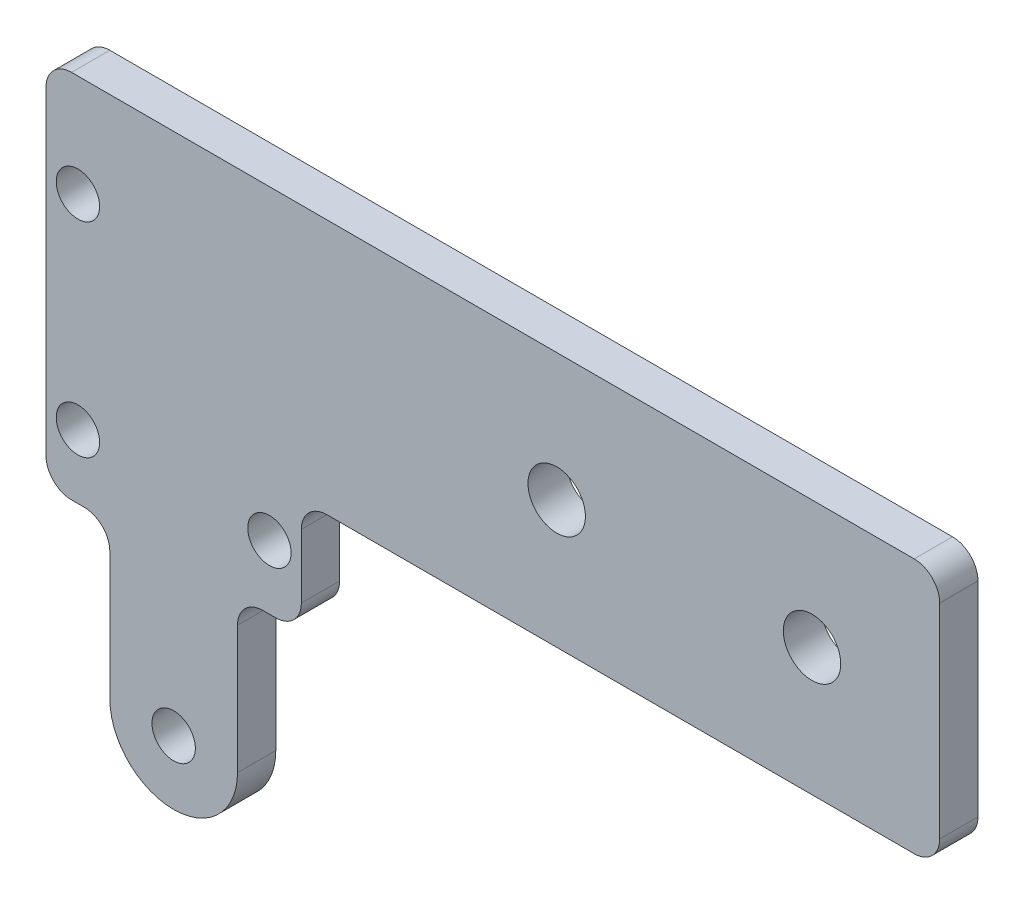
SolidWorks part; units mm, degrees
material "1023 Kohlenstoffstahlblech (SS)"
ref_plane "Ebene vorne" through (0, 0, 0) normal (0, 0, 1) x (1, 0, 0)
ref_plane "Ebene oben" through (0, 0, 0) normal (0, 1, 0) x (1, 0, 0)
ref_plane "Ebene rechts" through (0, 0, 0) normal (1, 0, 0) x (0, 0, -1)
sketch "Skizze1" plane through (0, 0, 0) normal (0, 0, 1) x (1, 0, 0)
  line L0 (0, 0) -> (0, -9)
  line L1 (0, -9) -> (-5, -9)
  line L2 (-5, -9) -> (-5, -21)
  line L3 (-15, -21) -> (-15, -9)
  line L4 (-15, -9) -> (-20, -9)
  line L5 (-20, -9) -> (-20, 20)
  line L6 (-20, 20) -> (50, 20)
  line L7 (50, 20) -> (50, 0)
  line L8 (50, 0) -> (0, 0)
  arc A0 (-15, -21) -> (-5, -21) centre (-10, -21) ccw
  dimension "D4" = 10
  dimension "D1" = 20
  dimension "D2" = 29
  dimension "D3" = 20
  dimension "D5" = 12
  dimension "D6" = 50
extrude "Aufsatz-Linear austragen1" add sketch "Skizze1" along normal blind 3
sketch "Skizze2" plane through (0, 0, 3) normal (0, 0, 1) x (1, 0, 0)
  arc A0 (-15, -21) -> (-5, -21) centre (-10, -21) ccw construction
  arc A1 (-15, -21) -> (-5, -21) centre (-10, -21) ccw construction
  circle A2 centre (-10, -21) radius 1.7
  dimension "D1" = 3.4
extrude "Schnitt-Linear austragen1" cut sketch "Skizze2" against normal through all
hole_wizard "Durchgangsloch für M41" positions "Skizze3" profile "Skizze5" hole size "M4" standard "ANSI Metrisch" end condition through all
sketch "Skizze3" plane through (0, 0, 3) normal (0, 0, 1) x (1, 0, 0)
  line L0 (50, 10) -> (40, 10) construction
  line L1 (50, 0) -> (50, 20) construction
  line L2 (40, 10) -> (20, 10) construction
  point P1 (40, 10)
  point P4 (20, 10)
  dimension "D1" = 10
  dimension "D2" = 20
sketch "Skizze5" plane through (20, 10, 3) normal (1, 0, 0) x (0, -1, 0)
  line L0 (0, 0) -> (0, 3)
  line L1 (0, 3) -> (2.25, 3)
  line L2 (2.25, 3) -> (2.25, 0)
  line L5 (2.25, 0) -> (0, 0)
  line L11 (0, -6.35) -> (0, 107.95) construction
  dimension "Bohrerdurchmesser" = 4.5
  dimension "Bohrungstiefe" = 3
hole_wizard "Durchgangsloch für M31" positions "Skizze7" profile "Skizze8" hole size "M3" standard "ANSI Metrisch" end condition through all
sketch "Skizze7" plane through (0, 0, 3) normal (0, 0, 1) x (1, 0, 0)
  line L1 (-17.5, 12) -> (-2.5, 12) construction
  line L2 (-17.5, 12) -> (-17.5, -4) construction
  line L3 (-17.5, -4) -> (-2.5, -4) construction
  line L4 (-2.5, 12) -> (-2.5, -4) construction
  line L5 (-10, -4) -> (-10, -26) construction
  arc A1 (-15, -21) -> (-5, -21) centre (-10, -21) ccw construction
  point P1 (-17.5, 12)
  point P2 (-2.5, -4)
  point P5 (-17.5, -4)
  dimension "D1" = 16
  dimension "D2" = 15
  dimension "D3" = 4
sketch "Skizze8" plane through (-17.5, 12, 3) normal (1, 0, 0) x (0, -1, 0)
  line L0 (0, 0) -> (0, 3)
  line L1 (0, 3) -> (1.7, 3)
  line L2 (1.7, 3) -> (1.7, 0)
  line L5 (1.7, 0) -> (0, 0)
  line L11 (0, -6.35) -> (0, 107.95) construction
  dimension "Bohrerdurchmesser" = 3.4
  dimension "Bohrungstiefe" = 3
fillet "Verrundung1" radius 2 8 edges at (-20, -9, 1.5) (-15, -9, 1.5) (-5, -9, 1.5) (0, -9, 1.5) (0, 0, 1.5) (50, 0, 1.5) (-20, 20, 1.5) (50, 20, 1.5)
sketch "Skizze9" [suppressed] plane through (0, 0, 3) normal (0, 0, 1) x (1, 0, 0)
  line L1 (-18, -9) -> (-2, -9)
  line L2 (-18, -9) -> (-18, -26)
  line L3 (-18, -26) -> (-2, -26)
  line L4 (-2, -9) -> (-2, -26)
  arc A0 (-15, -21) -> (-5, -21) centre (-10, -21) ccw construction
extrude "Schnitt-Linear austragen2" [suppressed] cut sketch "Skizze9" against normal through all
